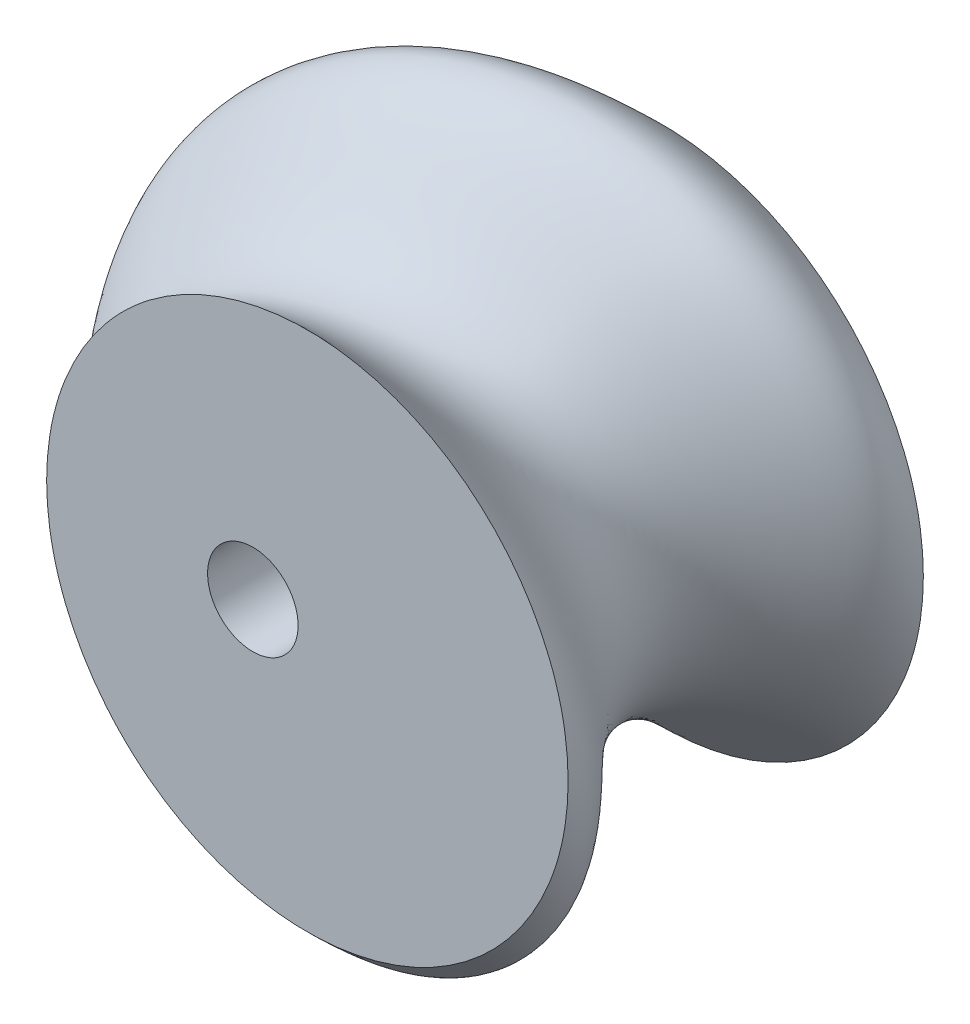
SolidWorks part; units mm, degrees
ref_plane "Ebene vorne" through (0, 0, 0) normal (0, 0, 1) x (1, 0, 0)
ref_plane "Ebene oben" through (0, 0, 0) normal (0, 1, 0) x (1, 0, 0)
ref_plane "Ebene rechts" through (0, 0, 0) normal (1, 0, 0) x (0, 0, -1)
sketch "Skizze2" plane through (0, 0, 0) normal (0, 0, 1) x (1, 0, 0)
  circle A0 centre (0, 0) radius 14.681
  dimension "D1" = 29.362
ref_plane "Ebene1" through (0, 0, 0) normal (0, 0, 1) x (1, 0, 0)
sketch "Skizze3" plane through (0, 0, 0) normal (0, 0, 1) x (1, 0, 0)
  circle A0 centre (-3.071, 0) radius 2.55
  point P0 (-3.071, 0)
  dimension "D2" = 5.1
  dimension "D1" = 3.071
curve "Spirale/Helix1" pitch 20 height 20 radius 2.55 centre (-3.071, 0, 0) axis (0, 0, 1) start towards (1, 0, 0)
sweep "Austragung1" add profiles "Skizze2" path "Spirale/Helix1"
sketch "Skizze5" plane through (0, 0, 20) normal (0, 0, 1) x (1, 0, 0)
  circle A0 centre (0, 0) radius 2.5
  dimension "D1" = 5
ref_plane "Ebene3" through (-0.521, 0, 0) normal (0, 0.6252, 0.7804) x (1, 0, 0)
extrude "Schnitt-Linear austragen2" cut sketch "Skizze3<2>" along normal blind 27
sketch "Skizze3<2>" plane through (0, 0, 0) normal (0, 0, 1) x (1, 0, 0) same geometry as "Skizze3"
ref_axis "Achse2" through (-3.071, 0, 20) along (0, 0, -1)
